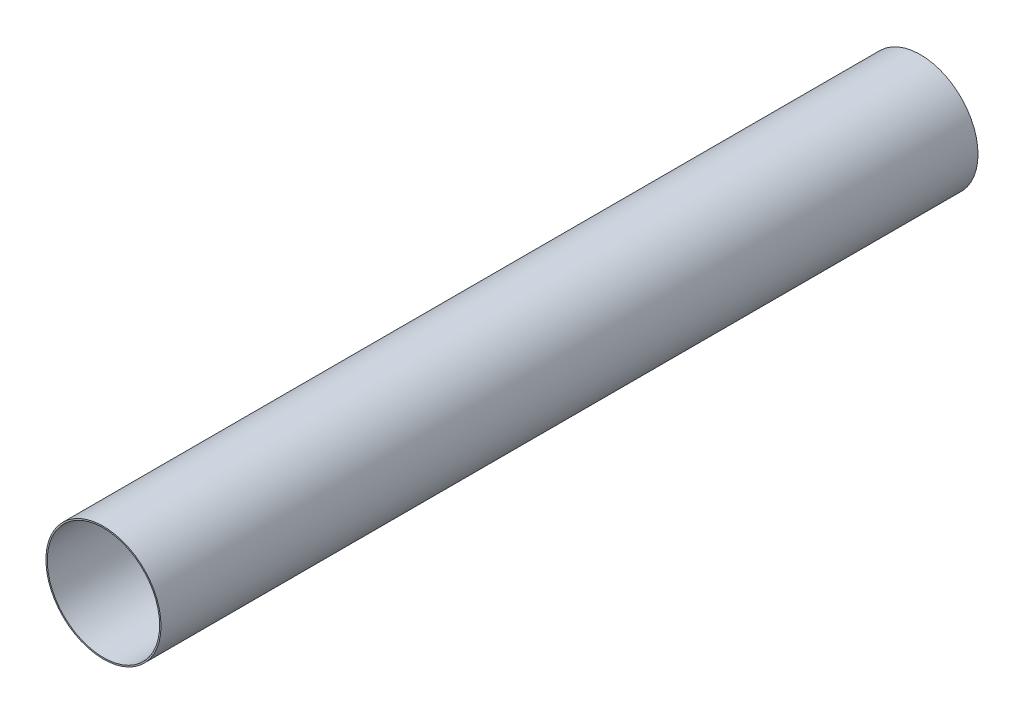
SolidWorks part; units mm, degrees
material "Thornel Mat VMA"
ref_plane "Front Plane" through (0, 0, 0) normal (0, 0, 1) x (1, 0, 0)
ref_plane "Top Plane" through (0, 0, 0) normal (0, 1, 0) x (1, 0, 0)
ref_plane "Right Plane" through (0, 0, 0) normal (1, 0, 0) x (0, 0, -1)
sketch "Sketch1" plane through (0, 0, 0) normal (0, 0, 1) x (1, 0, 0)
  circle A0 centre (0, 0) radius 84.55
  circle A1 centre (0, 0) radius 82.55
  dimension "D1" = 165.1
  dimension "D2" = 169.1
extrude "Boss-Extrude1" add sketch "Sketch1" along normal mid plane 1200
equation "\"TubeDiameter\" = 6.500in"
equation "\"D1@Sketch1\"=\"TubeDiameter\""
equation "\"D2@Sketch1\"=\"TubeDiameter\"+4mm"
